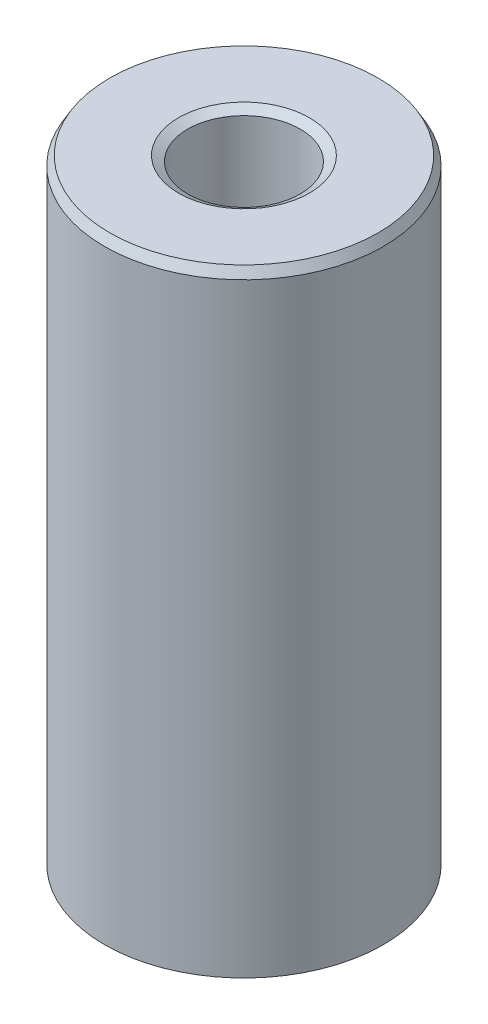
SolidWorks part; units mm, degrees
ref_plane "Front Plane" through (0, 0, 0) normal (0, 0, 1) x (1, 0, 0)
ref_plane "Top Plane" through (0, 0, 0) normal (0, 1, 0) x (1, 0, 0)
ref_plane "Right Plane" through (0, 0, 0) normal (1, 0, 0) x (0, 0, -1)
sketch "Sketch1" plane through (0, 0, 0) normal (0, 1, 0) x (1, 0, 0)
  circle A0 centre (0, 0) radius 12.5
  dimension "SLEEVE_OD" = 25
extrude "Boss-Extrude1" add sketch "Sketch1" along normal blind 55.4996
sketch "Sketch2" plane through (0, 0, 0) normal (0, 1, 0) x (1, 0, 0)
  circle A0 centre (0, 0) radius 5.0428
  dimension "BORE_D" = 10.0856
extrude "Cut-Extrude1" cut sketch "Sketch2" along normal through all
chamfer "Chamfer1" distance 0.8201 angle 30 4 edges at (0, 55.4996, 5.0428) (0, 0, 5.0428) (0, 0, 12.5) (0, 55.4996, 12.5) first distance on face at (0, 55.4996, 5.0428) first distance on face at (0, 0, 5.0428) first distance on face at (0, 55.4996, 12.5)
